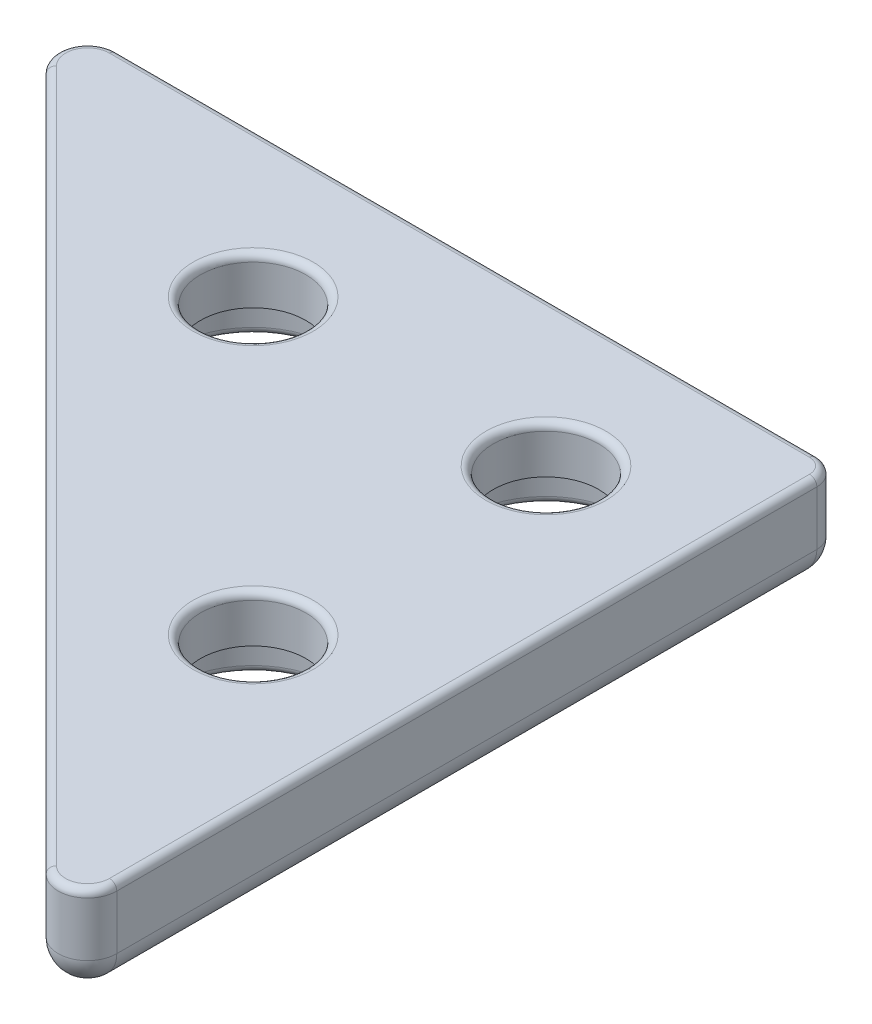
SolidWorks part; units mm, degrees
ref_plane "Front Plane" through (0, 0, 0) normal (0, 0, 1) x (1, 0, 0)
ref_plane "Top Plane" through (0, 0, 0) normal (0, 1, 0) x (1, 0, 0)
ref_plane "Right Plane" through (0, 0, 0) normal (1, 0, 0) x (0, 0, -1)
sketch "Sketch1" plane through (0, 0, 0) normal (0, 1, 0) x (1, 0, 0)
  line L0 (8.5, 10) -> (-39.3137, 10)
  line L1 (10, 8.5) -> (10, -39.3137)
  line L2 (-40.7279, 6.5858) -> (6.5858, -40.7279)
  line L3 (-20, 0) -> (-20, 10) construction
  line L4 (-20, 0) -> (-27.0711, -7.0711) construction
  circle A0 centre (0, 0) radius 3.6
  circle A1 centre (-20, 0) radius 3.6
  circle A2 centre (0, -20) radius 3.6
  arc A3 (10, -39.3137) -> (6.5858, -40.7279) centre (8, -39.3137) cw
  arc A4 (-39.3137, 10) -> (-40.7279, 6.5858) centre (-39.3137, 8) ccw
  circle A6 centre (-20, 0) radius 5.5
  circle A7 centre (0, 0) radius 5.5
  circle A8 centre (0, -20) radius 5.5
  arc A9 (10, 8.5) -> (8.5, 10) centre (8.5, 8.5) ccw
  point P19 (-44.1421, 10)
  point P22 (10, 10)
  dimension "D1" = 7.2
  dimension "D2" = 10
  dimension "D3" = 10
  dimension "D7" = 1.5
  dimension "D10" = 2
  dimension "D5" = 20
  dimension "D6" = 20
  dimension "D4" = 11
extrude "Boss-Extrude1" add sketch "Sketch1" along normal mid plane 6.2 contours L0 A4 L2 A3 L1 A8 A7 A6 | A6 A1 | A7 A0 | A8 A2 region at (-8.3201, 0, 8.3201) region at (-25.3444, 0, 0) region at (-5.3444, 0, 0) region at (-5.3444, 0, 20)
extrude "Cut-Extrude1" cut sketch "Sketch1<3>" along normal offset from surface (3 mm away) 3.2 from surface contours A6 A1 | A7 A0 | A8 A2 region at (-25.3444, 0, 0) region at (-5.3444, 0, 0) region at (-5.3444, 0, 20) up to face at (-7.5522, 3.1, 7.5522) starting at face at (-7.5522, -3.1, 7.5522)
sketch "Sketch1<3>" plane through (0, 0, 0) normal (0, 1, 0) x (1, 0, 0) same geometry as "Sketch1"
fillet "Fillet1" radius 2 6 edges at (-15.4069, -3.1, -10) (-41.1615, -3.1, -8.7654) (-17.0711, -3.1, 17.0711) (8.7654, -3.1, 41.1615) (10, -3.1, 15.4069) (9.5607, -3.1, -9.5607)
fillet "Fillet2" radius 0.5 12 edges at (10, 3.1, 15.4069) (8.7654, 3.1, 41.1615) (-17.0711, 3.1, 17.0711) (-41.1615, 3.1, -8.7654) (-15.4069, 3.1, -10) (0, 3.1, 23.6) (0, 3.1, 3.6) (-20, 3.1, 3.6) (-20, -3.1, 5.5) (0, -3.1, 5.5) (0, -3.1, 25.5) (9.5607, 3.1, -9.5607)
